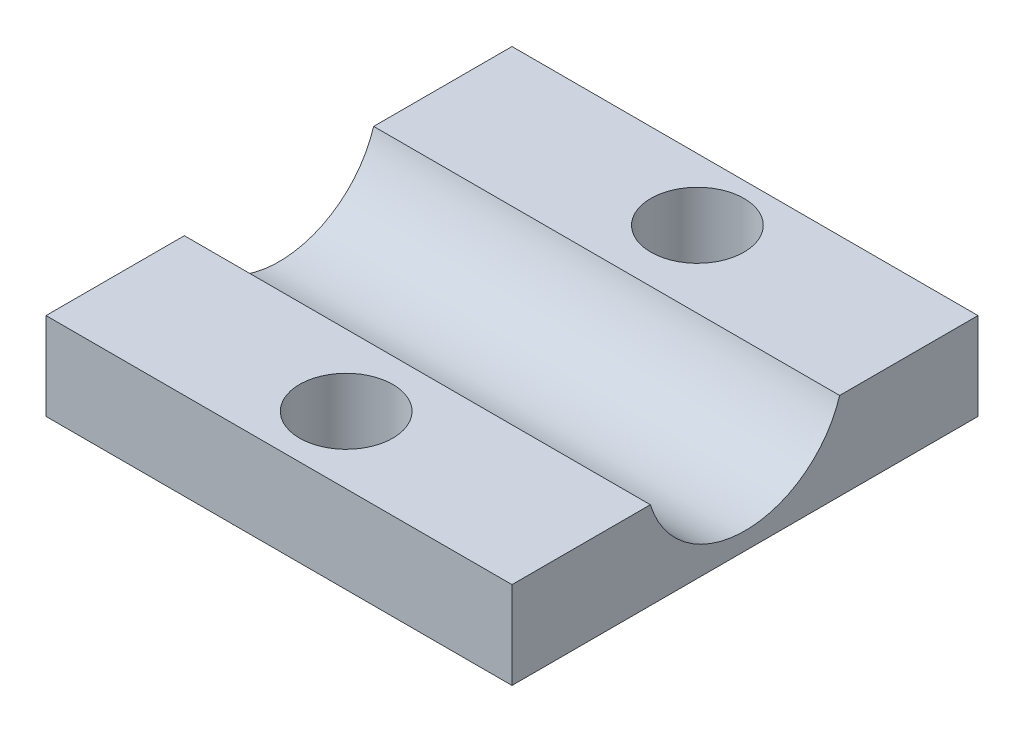
SolidWorks part; units mm, degrees
ref_plane "Front Plane" through (0, 0, 0) normal (0, 0, 1) x (1, 0, 0)
ref_plane "Top Plane" through (0, 0, 0) normal (0, 1, 0) x (1, 0, 0)
ref_plane "Right Plane" through (0, 0, 0) normal (1, 0, 0) x (0, 0, -1)
sketch "Sketch1" plane through (0, 0, 0) normal (0, 1, 0) x (1, 0, 0)
  line L1 (20, -20) -> (-20, -20)
  line L2 (20, -20) -> (20, 20)
  line L3 (20, 20) -> (-20, 20)
  line L4 (-20, -20) -> (-20, 20)
  line L5 (20, -20) -> (-20, 20) construction
  line L6 (20, 20) -> (-20, -20) construction
  point P0 (0, 0)
  dimension "D1" = 40
extrude "Boss-Extrude1" add sketch "Sketch1" along normal blind 7.5
sketch "Sketch2" plane through (0, 0, 0) normal (1, 0, 0) x (0, 0, -1)
  line L0 (20, 7.5) -> (-20, 7.5) construction
  circle A0 centre (0, 10) radius 8.5
  dimension "D2" = 17
  dimension "D3" = 2.5
  dimension "D1" = 10
extrude "Cut-Extrude1" cut sketch "Sketch2" against normal blind 20 and the other way blind 20
hole_wizard "Ø8.0 (8) Diameter Hole1" positions "Sketch3" profile "Sketch4" hole size "Ø8.0" standard "ISO" end condition through all
sketch "Sketch3" plane through (0, 7.5, 0) normal (0, 1, 0) x (1, 0, 0)
  point P0 (1.2472, 14.6672)
  point P2 (0, -14.2328)
  dimension "D1" = 28.9
sketch "Sketch4" plane through (1.2472, 7.5, -14.6672) normal (1, 0, 0) x (0, 0, 1)
  line L0 (0, 0) -> (0, 7.5)
  line L1 (0, 7.5) -> (4, 7.5)
  line L2 (4, 7.5) -> (4, 0)
  line L5 (4, 0) -> (0, 0)
  line L11 (0, -6.35) -> (0, 107.95) construction
  dimension "Thru Hole Dia." = 8
  dimension "Thru Hole Depth" = 7.5
